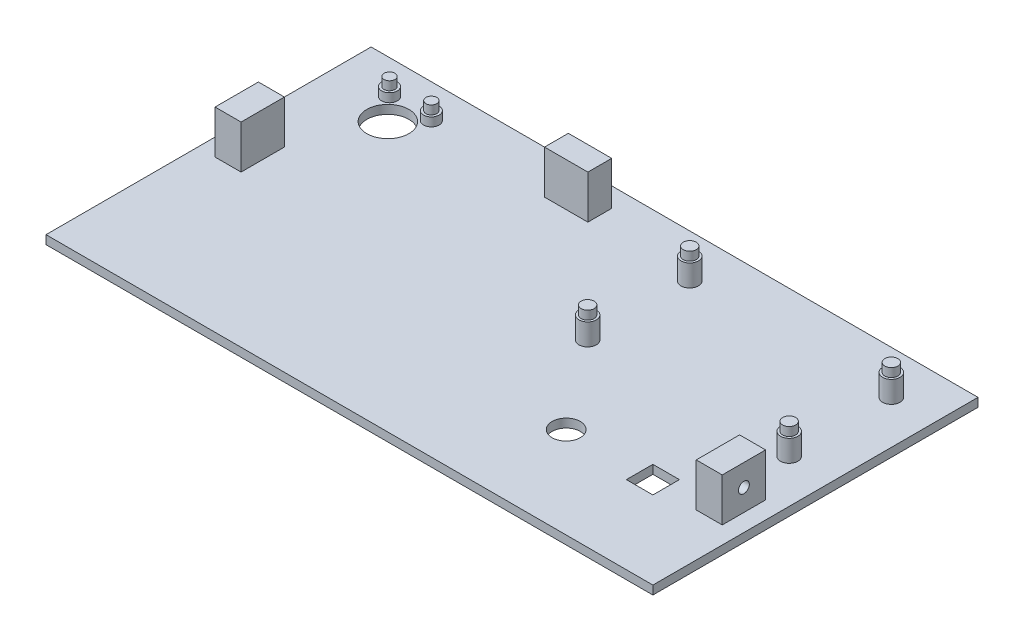
SolidWorks part; units mm, degrees
ref_plane "前视基准面" through (0, 0, 0) normal (0, 0, 1) x (1, 0, 0)
ref_plane "上视基准面" through (0, 0, 0) normal (0, 1, 0) x (1, 0, 0)
ref_plane "右视基准面" through (0, 0, 0) normal (1, 0, 0) x (0, 0, -1)
other "Configuration Table"
sketch "草图1" plane through (0, 0, 0) normal (0, 1, 0) x (1, 0, 0)
  line L1 (70, -37.5) -> (-70, -37.5)
  line L2 (70, -37.5) -> (70, 37.5)
  line L3 (70, 37.5) -> (-70, 37.5)
  line L4 (-70, -37.5) -> (-70, 37.5)
  line L5 (70, -37.5) -> (-70, 37.5) construction
  line L6 (70, 37.5) -> (-70, -37.5) construction
  point P0 (0, 0)
  dimension "D1" = 75
  dimension "D2" = 140
extrude "凸台-拉伸1" add sketch "草图1" along normal blind 2
sketch "草图4" plane through (0, 2, 0) normal (0, 1, 0) x (1, 0, 0)
  circle A0 centre (-53.1699, 24.5319) radius 4.85
  dimension "D1" = 9.7
extrude "切除-拉伸1" cut sketch "草图4" against normal through all
sketch "草图5" plane through (0, 2, 0) normal (0, 1, 0) x (1, 0, 0)
  line L0 (-53.1699, 24.5319) -> (-53.1699, 29.7419) construction
  line L1 (-53.1699, 29.7419) -> (-57.9999, 29.7419) construction
  line L2 (-53.1699, 29.7419) -> (-48.3479, 29.7419) construction
  line L3 (70, 37.5) -> (-70, 37.5) construction
  circle A2 centre (-57.9999, 29.7419) radius 1.8
  circle A3 centre (-48.3479, 29.7419) radius 1.8
  dimension "D1" = 5.21
  dimension "D2" = 9.652
extrude "凸台-拉伸2" add sketch "草图5" along normal blind 2
sketch "草图13" plane through (0, 4, 0) normal (0, 1, 0) x (1, 0, 0)
  circle A0 centre (-57.9999, 29.7419) radius 1.25
  circle A1 centre (-48.3479, 29.7419) radius 1.25
sketch "草图18" plane through (0, 2, 0) normal (0, 1, 0) x (1, 0, 0)
  line L0 (70, -37.5) -> (70, 37.5) construction
  line L1 (45.88, -13.38) -> (52, -13.38)
  line L2 (45.88, -13.38) -> (45.88, -19.5)
  line L3 (45.88, -19.5) -> (52, -19.5)
  line L4 (52, -13.38) -> (52, -19.5)
  line L5 (-70, -37.5) -> (70, -37.5) construction
  dimension "D1" = 6.12
  dimension "D2" = 6.12
  dimension "D3" = 18
  dimension "D4" = 18
extrude "切除-拉伸3" cut sketch "草图18" against normal blind 4
sketch "草图19" plane through (0, 2, 0) normal (0, 1, 0) x (1, 0, 0)
  line L6 (48.94, -16.44) -> (28.94, -16.44) construction
  circle A0 centre (28.94, -16.44) radius 3.25
  dimension "D2" = 6.5
  dimension "D1" = 20
extrude "切除-拉伸4" cut sketch "草图19" against normal blind 4
sketch "草图21" plane through (0, 2, 0) normal (0, 1, 0) x (1, 0, 0)
  line L0 (70, 37.5) -> (-70, 37.5) construction
  line L2 (70, -37.5) -> (70, 37.5) construction
  circle A0 centre (60, 27.5) radius 2
  circle A1 centre (60, 3.95) radius 2
  circle A2 centre (13.5, 27.5) radius 2
  circle A3 centre (13.5, 3.95) radius 2
  dimension "D1" = 10
  dimension "D3" = 23.55
  dimension "D2" = 10
  dimension "D4" = 46.5
extrude "凸台-拉伸3" add sketch "草图21" along normal blind 5
sketch "草图22" plane through (0, 7, 0) normal (0, 1, 0) x (1, 0, 0)
  circle A0 centre (13.5, 27.5) radius 1.5
  circle A1 centre (60, 27.5) radius 1.5
  circle A2 centre (13.5, 3.95) radius 1.5
  circle A3 centre (60, 3.95) radius 1.5
extrude "凸台-拉伸4" add sketch "草图13" along normal blind 2
extrude "凸台-拉伸5" add sketch "草图22" along normal blind 2
sketch "草图26" plane through (-70, 0, 0) normal (-1, 0, 0) x (0, 0, 1)
  line L6 (-37.5, 2) -> (37.5, 2) construction
  line L7 (-7.5, 2) -> (2.5, 2)
  line L8 (-7.5, 2) -> (-7.5, 12)
  line L9 (-7.5, 12) -> (2.5, 12)
  line L10 (2.5, 2) -> (2.5, 12)
  line L11 (-37.5, 2) -> (-37.5, 0) construction
  dimension "D1" = 30
  dimension "D2" = 10
  dimension "D3" = 10
extrude "凸台-拉伸6" add sketch "草图26" against normal blind 10
sketch "草图27" plane through (-70, 0, 0) normal (-1, 0, 0) x (0, 0, 1)
  line L9 (-7.5, 2) -> (2.5, 2)
  line L10 (-7.5, 2) -> (-7.5, 12)
  line L11 (-7.5, 12) -> (2.5, 12)
  line L12 (2.5, 2) -> (2.5, 12)
extrude "切除-拉伸5" cut sketch "草图27" against normal blind 4
sketch "草图28" plane through (-66, 0, 0) normal (-1, 0, 0) x (0, 0, 1)
  line L0 (-7.5, 2) -> (2.5, 2) construction
  point P0 (-2.5, 7)
  point P1 (0, 0)
  dimension "D1" = 5
hole_wizard "M3 螺纹孔1" positions "3D草图2" profile "草图29" tap size "M3" standard "ISO"
sketch3d "3D草图2"
  point P0 (-66, 7, -2.5)
sketch "草图29" plane through (-66, 7, -2.5) normal (0, 1, 0) x (0, 0, 1)
  line L0 (0, 0) -> (0, 4.7511)
  line L1 (0, 4.7511) -> (1.25, 4)
  line L2 (1.25, 4) -> (1.25, 0)
  line L5 (1.25, 0) -> (0, 0)
  line L10 (0, 4.7511) -> (-1.25, 4) construction
  line L11 (0, -6.35) -> (0, 107.95) construction
  dimension "螺纹孔钻头直径" = 2.5
  dimension "螺纹孔钻头深度" = 4
  dimension "导头角度" = 118
cosmetic thread "孔螺蚊线2" parameters "D1"=6, "D2"=3
sketch "草图30" plane through (70, 0, 0) normal (1, 0, 0) x (0, 0, -1)
  line L0 (-37.5, 2) -> (37.5, 2) construction
  line L1 (-17.5, 2) -> (-7.5, 2)
  line L2 (-17.5, 2) -> (-17.5, 12)
  line L3 (-17.5, 12) -> (-7.5, 12)
  line L4 (-7.5, 2) -> (-7.5, 12)
  line L5 (-37.5, 2) -> (-37.5, 0) construction
  dimension "D1" = 10
  dimension "D2" = 20
  dimension "D3" = 10
extrude "凸台-拉伸7" add sketch "草图30" against normal blind 10
sketch "草图31" plane through (70, 0, 0) normal (1, 0, 0) x (0, 0, -1)
  line L1 (-17.5, 12) -> (-7.5, 12)
  line L2 (-17.5, 12) -> (-17.5, 2)
  line L3 (-17.5, 2) -> (-7.5, 2)
  line L4 (-7.5, 12) -> (-7.5, 2)
extrude "切除-拉伸6" cut sketch "草图31" against normal blind 4
sketch "草图32" plane through (66, 0, 0) normal (1, 0, 0) x (0, 0, -1)
  line L0 (-7.5, 12) -> (-17.5, 12) construction
  point P0 (-12.5, 7)
  point P1 (0, 0)
  dimension "D1" = 5
hole_wizard "M3 螺纹孔2" positions "3D草图3" profile "草图33" tap size "M3" standard "ISO"
sketch3d "3D草图3"
  point P0 (66, 7, 12.5)
sketch "草图33" plane through (66, 7, 12.5) normal (0, 1, 0) x (0, 0, -1)
  line L0 (0, 0) -> (0, 4.7511)
  line L1 (0, 4.7511) -> (1.25, 4)
  line L2 (1.25, 4) -> (1.25, 0)
  line L5 (1.25, 0) -> (0, 0)
  line L10 (0, 4.7511) -> (-1.25, 4) construction
  line L11 (0, -6.35) -> (0, 107.95) construction
  dimension "螺纹孔钻头直径" = 2.5
  dimension "螺纹孔钻头深度" = 4
  dimension "导头角度" = 118
cosmetic thread "孔螺蚊线3" parameters "D1"=6, "D2"=3
sketch "草图34" plane through (0, 0, -37.5) normal (0, 0, -1) x (-1, 0, 0)
  line L0 (-70, 2) -> (70, 2) construction
  line L1 (10, 2) -> (20, 2)
  line L2 (10, 2) -> (10, 12)
  line L3 (10, 12) -> (20, 12)
  line L4 (20, 2) -> (20, 12)
  line L5 (70, 2) -> (70, 0) construction
  dimension "D1" = 10
  dimension "D2" = 50
  dimension "D3" = 10
extrude "凸台-拉伸8" add sketch "草图34" against normal blind 10
sketch "草图35" plane through (0, 0, -37.5) normal (0, 0, -1) x (-1, 0, 0)
  line L1 (10, 2) -> (20, 2)
  line L2 (10, 2) -> (10, 12)
  line L3 (10, 12) -> (20, 12)
  line L4 (20, 2) -> (20, 12)
extrude "切除-拉伸7" cut sketch "草图35" against normal blind 4.5
sketch "草图36" plane through (0, 0, -33) normal (0, 0, -1) x (-1, 0, 0)
  line L0 (10, 2) -> (20, 2) construction
  point P0 (15, 7)
  dimension "D1" = 5
hole_wizard "M3 螺纹孔3" positions "3D草图4" profile "草图37" tap size "M3" standard "ISO"
sketch3d "3D草图4"
  point P0 (-15, 7, -33)
sketch "草图37" plane through (-15, 7, -33) normal (1, 0, 0) x (0, 1, 0)
  line L0 (0, 0) -> (0, 4.7511)
  line L1 (0, 4.7511) -> (1.25, 4)
  line L2 (1.25, 4) -> (1.25, 0)
  line L5 (1.25, 0) -> (0, 0)
  line L10 (0, 4.7511) -> (-1.25, 4) construction
  line L11 (0, -6.35) -> (0, 107.95) construction
  dimension "螺纹孔钻头直径" = 2.5
  dimension "螺纹孔钻头深度" = 4
  dimension "导头角度" = 118
cosmetic thread "孔螺蚊线4" parameters "D1"=6, "D2"=3
